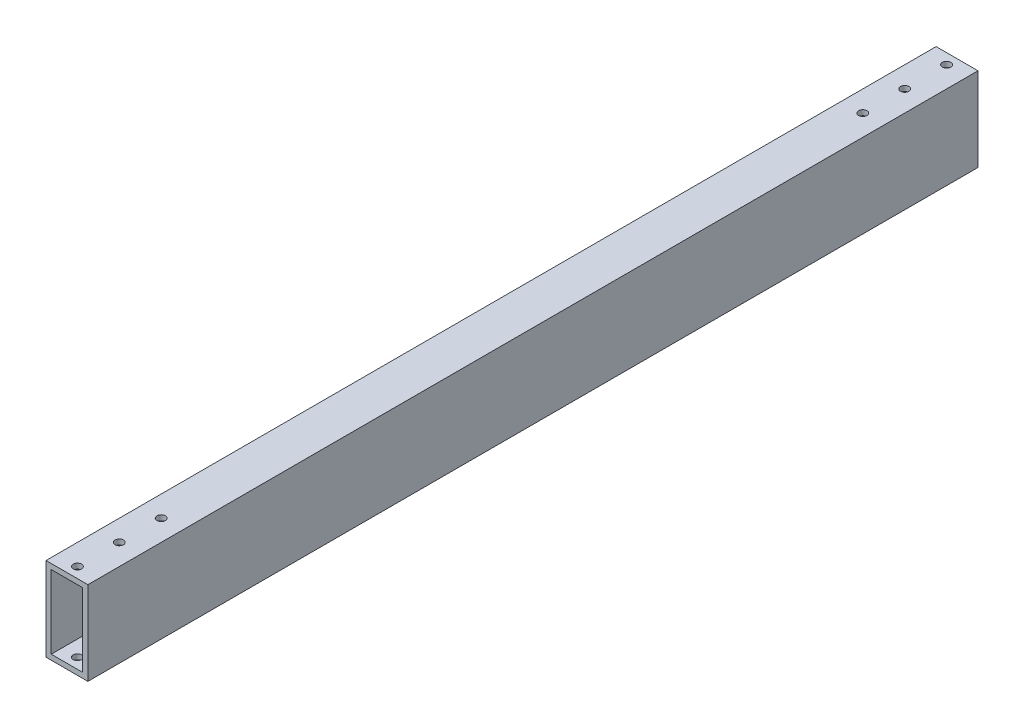
SolidWorks part; units mm, degrees
material "6061-T6 (SS)"
ref_plane "Front" through (0, 0, 0) normal (0, 0, 1) x (1, 0, 0)
ref_plane "Top" through (0, 0, 0) normal (0, 1, 0) x (1, 0, 0)
ref_plane "Right" through (0, 0, 0) normal (1, 0, 0) x (0, 0, -1)
sketch "Sketch1" plane through (0, 0, 0) normal (0, 0, 1) x (1, 0, 0)
  line L1 (-12.7, -25.4) -> (12.7, -25.4)
  line L2 (-12.7, -25.4) -> (-12.7, 25.4)
  line L3 (-12.7, 25.4) -> (12.7, 25.4)
  line L4 (12.7, -25.4) -> (12.7, 25.4)
  line L5 (-12.7, -25.4) -> (12.7, 25.4) construction
  line L6 (-12.7, 25.4) -> (12.7, -25.4) construction
  point P0 (0, 0)
  dimension "D1" = 25.4
  dimension "D2" = 50.8
extrude "Extrude-Thin1" add sketch "Sketch1" along normal blind 539.75 thin thin type one direction reverse wall 3.175
hole_wizard "#10 Clearance Hole1" positions "Sketch2" profile "Sketch3" hole size "#10" standard "ANSI Inch" end condition through all
sketch "Sketch2" plane through (0, 25.4, 0) normal (0, 1, 0) x (1, 0, 0)
  line L0 (-12.7, -539.75) -> (-12.7, 0) construction
  line L1 (12.7, -539.75) -> (-12.7, -539.75) construction
  point P0 (0, -533.4)
  point P2 (0, -508)
  point P4 (0, -482.6)
  point P6 (0, -6.35)
  point P8 (0, -31.75)
  point P10 (0, -57.15)
  dimension "D1" = 12.7
  dimension "D2" = 25.4
  dimension "D3" = 6.35
  dimension "D4" = 25.4
  dimension "D5" = 6.35
  dimension "D6" = 25.4
  dimension "D7" = 25.4
sketch "Sketch3" plane through (0, 25.4, 533.4) normal (1, 0, 0) x (0, 0, 1)
  line L0 (0, 0) -> (0, 50.8)
  line L1 (0, 50.8) -> (2.5527, 50.8)
  line L2 (2.5527, 50.8) -> (2.5527, 0)
  line L5 (2.5527, 0) -> (0, 0)
  line L11 (0, -6.35) -> (0, 107.95) construction
  dimension "Thru Hole Dia." = 5.1054
  dimension "Thru Hole Depth" = 50.8
sketch "Sketch6" plane through (-12.7, 0, 0) normal (-1, 0, 0) x (0, 0, 1)
  point P0 (148.968, 0)
  point P3 (88.968, 0)
  point P6 (28.968, 0)
  point P9 (208.968, 0)
  point P12 (268.968, 0)
  point P15 (328.968, 0)
  point P18 (388.968, 0)
  point P21 (448.968, 0)
  point P24 (508.968, 0)
hole_wizard "M4x0.7 Tapped Hole1" positions "Sketch6" profile "Sketch5" tap size "M4x0.7" standard "ANSI Metric" end condition up to next
cosmetic thread "Hole Thread1" parameters "D2"=4
cosmetic thread "Hole Thread2" parameters "D2"=4
cosmetic thread "Hole Thread3" parameters "D2"=4
cosmetic thread "Hole Thread4" parameters "D2"=4
cosmetic thread "Hole Thread5" parameters "D2"=4
cosmetic thread "Hole Thread6" parameters "D2"=4
cosmetic thread "Hole Thread7" parameters "D2"=4
cosmetic thread "Hole Thread8" parameters "D2"=4
cosmetic thread "Hole Thread9" parameters "D2"=4
sketch "Sketch5" plane through (-12.7, 0, 148.968) normal (0, 1, 0) x (0, 0, 1)
  line L0 (0, 0) -> (0, 3.175)
  line L1 (0, 3.175) -> (1.65, 3.175)
  line L2 (1.65, 3.175) -> (1.65, 0)
  line L5 (1.65, 0) -> (0, 0)
  line L11 (0, -6.35) -> (0, 107.95) construction
  dimension "Thru Tap Drill Dia." = 3.3
  dimension "Thru Tap Drill Depth" = 3.175
sketch "Sketch9" plane through (0, -25.4, 0) normal (0, -1, 0) x (-1, 0, 0)
  circle A1 centre (3.175, -298.958) radius 1.651 construction
  point P0 (3.175, -70.358)
  point P3 (-3.175, -95.758)
  point P6 (3.175, -127.508)
  point P9 (-3.175, -152.908)
  point P12 (3.175, -184.658)
  point P19 (3.175, -241.808)
  point P22 (-3.175, -267.208)
  point P25 (2.8902, -300.5843)
  point P29 (-3.175, -324.358)
  point P32 (3.175, -356.108)
  point P35 (-3.175, -381.508)
  point P38 (3.175, -413.258)
  point P41 (-3.175, -438.658)
  point P44 (3.175, -470.408)
  point P50 (-3.175, -210.058)
hole_wizard "1/8 (0.13) Diameter Hole1" positions "Sketch9" profile "Sketch8" hole size "1/8" standard "ANSI Inch" end condition up to next
sketch "Sketch8" plane through (-3.175, -25.4, 70.358) normal (1, 0, 0) x (0, 0, -1)
  line L0 (0, 0) -> (0, 3.175)
  line L1 (0, 3.175) -> (1.651, 3.175)
  line L2 (1.651, 3.175) -> (1.651, 0)
  line L5 (1.651, 0) -> (0, 0)
  line L11 (0, -6.35) -> (0, 107.95) construction
  dimension "Thru Hole Dia." = 3.302
  dimension "Thru Hole Depth" = 3.175
